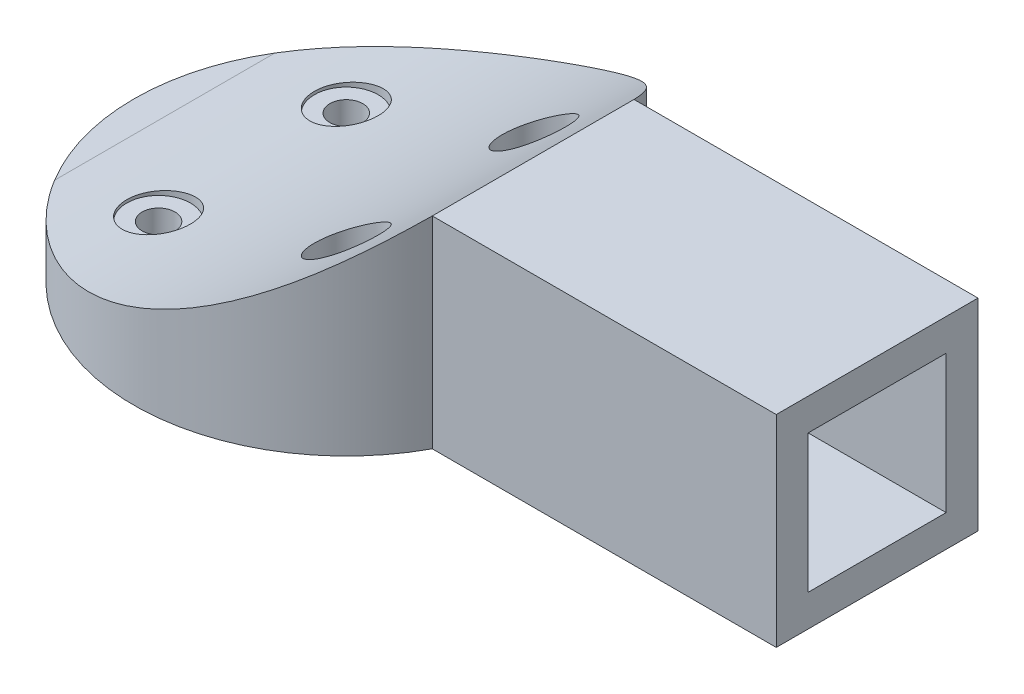
SolidWorks part; units mm, degrees
ref_plane "Front Plane" through (0, 0, 0) normal (0, 0, 1) x (1, 0, 0)
ref_plane "Top Plane" through (0, 0, 0) normal (0, 1, 0) x (1, 0, 0)
ref_plane "Right Plane" through (0, 0, 0) normal (1, 0, 0) x (0, 0, -1)
sketch "Sketch1" plane through (0, 0, 0) normal (0, 1, 0) x (1, 0, 0)
  line L0 (17.5997, 9.5) -> (50, 9.5)
  line L1 (0, -44.7868) -> (0, 44.7868) construction
  line L2 (50, 9.5) -> (50, -9.5)
  line L3 (50, -9.5) -> (17.5997, -9.5)
  line L4 (-44.2539, 0) -> (44.2539, 0) construction
  arc A0 (17.5997, 9.5) -> (17.5997, -9.5) centre (0, 0) ccw
  dimension "D1" = 20
  dimension "D2" = 19
  dimension "D3" = 9.5
  dimension "D4" = 50
extrude "Boss-Extrude1" add sketch "Sketch1" along normal mid plane 5
sketch "Sketch2" plane through (0, 0, 0) normal (0, 1, 0) x (1, 0, 0)
  line L0 (-15.679, 15.679) -> (15.679, -15.679) construction
  line L2 (14.5557, 14.5557) -> (-14.5557, -14.5557) construction
  line L3 (-44.2539, 0) -> (44.2539, 0) construction
  circle A0 centre (0, 0) radius 12.5
  circle A1 centre (8.8388, 8.8388) radius 1.55
  circle A2 centre (-8.8388, 8.8388) radius 1.55
  circle A3 centre (-8.8388, -8.8388) radius 1.55
  circle A4 centre (8.8388, -8.8388) radius 1.55
  dimension "D1" = 25
  dimension "D2" = 3.1
  dimension "D3" = 45
  dimension "D4" = 90
extrude "Cut-Extrude1" cut sketch "Sketch2" against normal mid plane 5 contours A2 | A3 | A1 | A4
sketch "Sketch4" plane through (0, 0, 0) normal (0, 1, 0) x (1, 0, 0)
  line L0 (17.5997, 21.3665) -> (17.5997, -21.3073) construction
ref_plane "Plane1" through (17.5997, 0, 0) normal (-1, 0, 0) x (0, 0, 1)
sketch "Sketch6" plane through (50, 0, 0) normal (1, 0, 0) x (0, 0, -1)
  line L1 (-9.5, -2.5) -> (9.5, -2.5)
  line L2 (-9.5, -2.5) -> (-9.5, 16.5)
  line L3 (-9.5, 16.5) -> (9.5, 16.5)
  line L4 (9.5, -2.5) -> (9.5, 16.5)
extrude "Boss-Extrude3" add sketch "Sketch6" against normal up to surface (32.4003 mm away) up to plane "Plane1"
sketch "Sketch8" plane through (50, 0, 0) normal (1, 0, 0) x (0, 0, -1)
  line L1 (-6.5, 13.5) -> (6.5, 13.5)
  line L2 (-6.5, 13.5) -> (-6.5, 0.5)
  line L3 (-6.5, 0.5) -> (6.5, 0.5)
  line L4 (6.5, 13.5) -> (6.5, 0.5)
  line L5 (9.5, 16.5) -> (-9.5, 16.5) construction
  line L6 (9.5, 16.5) -> (9.5, -2.5) construction
  dimension "D1" = 13
  dimension "D2" = 3
  dimension "D3" = 3
extrude "Cut-Extrude2" cut sketch "Sketch8" against normal offset from surface (27.4003 mm away) 5 up to face at (17.5997, 9.5, 0)
fillet "Fillet2" radius 50 1 edges at (17.5997, 2.5, 0)
sketch "Sketch13" plane through (0, 2.5, 0) normal (0, 1, 0) x (1, 0, 0)
  circle A0 centre (-8.8388, 8.8388) radius 3
  circle A1 centre (8.8388, 8.8388) radius 3
  circle A2 centre (-8.8388, -8.8388) radius 3
  circle A3 centre (8.8388, -8.8388) radius 3
  dimension "D1" = 6
extrude "Cut-Extrude4" cut sketch "Sketch13" along normal up to surface (0.687 mm away) up to face at (-0.4962, 7.2904, -0.0013)
